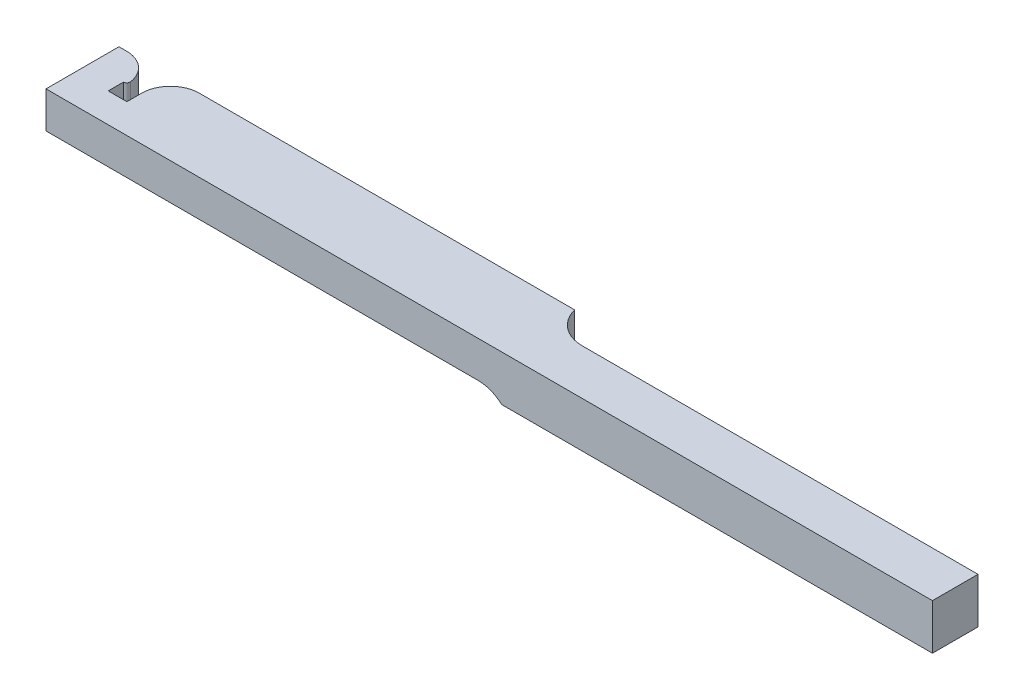
SolidWorks part; units mm, degrees
ref_plane "Front Plane" through (0, 0, 0) normal (0, 0, 1) x (1, 0, 0)
ref_plane "Top Plane" through (0, 0, 0) normal (0, 1, 0) x (1, 0, 0)
ref_plane "Right Plane" through (0, 0, 0) normal (1, 0, 0) x (0, 0, -1)
sketch "Sketch1" plane through (0, 0, 0) normal (1, 0, 0) x (0, 0, -1)
  line L1 (0, 0) -> (10.16, 0)
  line L2 (0, 0) -> (0, 5.08)
  line L3 (0, 5.08) -> (10.16, 5.08)
  line L4 (10.16, 0) -> (10.16, 5.08)
  dimension "D1" = 5.08
  dimension "D2" = 10.16
extrude "Boss-Extrude1" add sketch "Sketch1" along normal blind 63.5
sketch "Sketch2" plane through (0, 5.08, 0) normal (0, 1, 0) x (1, 0, 0)
  line L0 (63.5, 10.16) -> (0, 10.16) construction
  line L1 (5.08, 10.16) -> (7.1882, 10.16)
  line L2 (5.08, 10.16) -> (5.08, 4.086)
  line L3 (5.08, 4.086) -> (7.1882, 4.086)
  line L4 (7.1882, 10.16) -> (7.1882, 4.086)
  line L5 (0, 10.16) -> (0, 0) construction
  dimension "D1" = 5.08
  dimension "D2" = 6.074
  dimension "D3" = 2.1082
extrude "Cut-Extrude1" cut sketch "Sketch2" against normal blind 6
sketch "Sketch3" plane through (0, 5.08, 0) normal (0, 1, 0) x (1, 0, 0)
  line L1 (5.08, 4.086) -> (4.58, 4.086)
  line L2 (5.08, 4.086) -> (5.08, 6.1942)
  line L3 (5.08, 6.1942) -> (4.58, 6.1942)
  line L4 (4.58, 4.086) -> (4.58, 6.1942)
  dimension "D1" = 2.1082
  dimension "D2" = 0.5
extrude "Cut-Extrude2" cut sketch "Sketch3" against normal blind 6
sketch "Sketch4" plane through (63.5, 0, 0) normal (1, 0, 0) x (0, 0, -1)
  line L1 (0, 0) -> (6.35, 0)
  line L2 (0, 0) -> (0, 6.35)
  line L3 (0, 6.35) -> (6.35, 6.35)
  line L4 (6.35, 0) -> (6.35, 6.35)
  dimension "D1" = 6.35
  dimension "D2" = 6.35
extrude "Boss-Extrude2" add sketch "Sketch4" along normal blind 60
fillet "Fillet3" radius 4 2 edges at (7.1882, 2.54, -10.16) (5.08, 2.54, -10.16)
fillet "Fillet4" radius 0.5 1 edges at (5.08, 2.54, -6.1942)
fillet "Fillet6" radius 5 1 edges at (63.5, 5.08, -3.175)
fillet "Fillet10" radius 5 1 edges at (63.5, 2.54, -6.35)
mirror "Mirror1" about plane through (63.5, 0, 0) normal (0, 1, 0) of bodies 104 108
delete or keep bodies "Body-Delete/Keep 1" type delete bodies bodies 104
